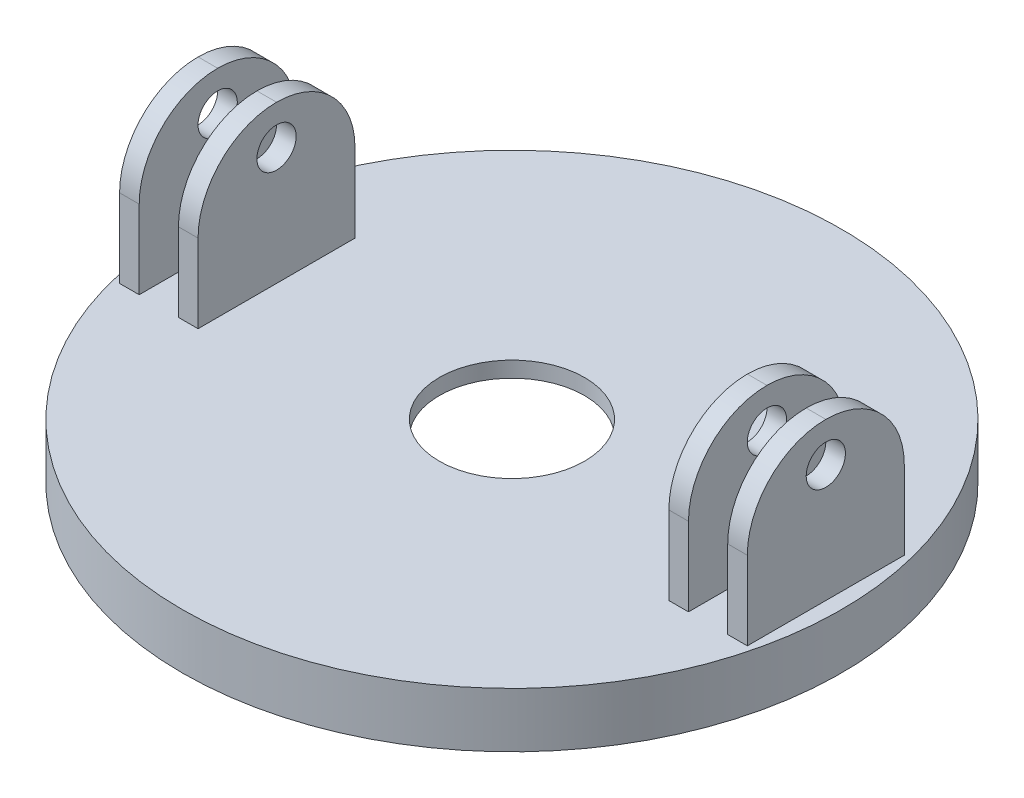
SolidWorks part; units mm, degrees
ref_plane "Alzado" through (0, 0, 0) normal (0, 0, 1) x (1, 0, 0)
ref_plane "Planta" through (0, 0, 0) normal (0, 1, 0) x (1, 0, 0)
ref_plane "Vista lateral" through (0, 0, 0) normal (1, 0, 0) x (0, 0, -1)
sketch "Croquis1" plane through (0, 0, 0) normal (0, 1, 0) x (1, 0, 0)
  circle A0 centre (0, 0) radius 84
  circle A1 centre (0, 0) radius 82
  dimension "D1" = 168
  dimension "D2" = 164
extrude "Saliente-Extruir1" add sketch "Croquis1" along normal blind 10
sketch "Croquis2" plane through (0, 10, 0) normal (0, 1, 0) x (1, 0, 0)
  circle A0 centre (0, 0) radius 84
  dimension "D1" = 168
extrude "Saliente-Extruir2" add sketch "Croquis2" along normal blind 4
sketch "Croquis3" plane through (0, 10, 0) normal (0, -1, 0) x (1, 0, 0)
  circle A0 centre (-20, 40) radius 1.5
  dimension "D1" = 3
  dimension "D6" = 40
  dimension "D7" = 20
extrude "Saliente-Extruir3" add sketch "Croquis3" along normal blind 10
ref_axis "Eje1" through (0, -0.7, 0) along (0, 1, 0)
pattern_circular "MatrizC1" count 4 every 90 about axis through (0, -0.7, 0) along (0, 1, 0) of "Saliente-Extruir3"
sketch "Croquis15" plane through (0, 0, 0) normal (0, -1, 0) x (1, 0, 0)
  circle A0 centre (0, 0) radius 82
  circle A1 centre (0, 0) radius 83
  dimension "D1" = 164
  dimension "D2" = 166
extrude "Cortar-Extruir1" cut sketch "Croquis15" against normal blind 5
sketch "Croquis16" plane through (0, 10, 0) normal (0, -1, 0) x (1, 0, 0)
  circle A0 centre (0, 0) radius 18.5
  dimension "D1" = 37
extrude "Cortar-Extruir2" cut sketch "Croquis16" against normal blind 13 contours A0
sketch "Croquis18" plane through (0, 14, 0) normal (0, 1, 0) x (1, 0, 0)
  line L0 (0, 0) -> (-84, 0) construction
  line L1 (0, 0) -> (0, 84) construction
  line L3 (-80, -20) -> (-60, -20)
  line L4 (-80, -20) -> (-80, 20)
  line L5 (-80, 20) -> (-60, 20)
  line L6 (-60, -20) -> (-60, 20)
  line L7 (-80, -20) -> (-60, 20) construction
  line L8 (-80, 20) -> (-60, -20) construction
  circle A0 centre (0, 0) radius 84 construction
  point P6 (-70, 0)
  dimension "D1" = 20
  dimension "D2" = 40
  dimension "D3" = 60
extrude "Saliente-Extruir4" add sketch "Croquis18" along normal blind 40
sketch "Croquis19" plane through (0, 54, 0) normal (0, 1, 0) x (1, 0, 0)
  line L0 (-60, 20) -> (-80, 20) construction
  line L1 (-75, 20) -> (-65, 20)
  line L2 (-75, 20) -> (-75, -20)
  line L3 (-75, -20) -> (-65, -20)
  line L4 (-65, 20) -> (-65, -20)
  line L5 (-80, -20) -> (-60, -20) construction
  line L6 (-80, 20) -> (-80, -20) construction
  dimension "D2" = 10
  dimension "D3" = 5
extrude "Cortar-Extruir3" cut sketch "Croquis19" against normal blind 40
sketch "Croquis20" plane through (-80, 0, 0) normal (-1, 0, 0) x (0, 0, 1)
  line L0 (-20, 54) -> (20, 54) construction
  line L1 (-20, 54) -> (-20, 14) construction
  circle A0 centre (0, 44) radius 5
  dimension "D3" = 10
  dimension "D1" = 10
  dimension "D2" = 20
extrude "Cortar-Extruir4" cut sketch "Croquis20" against normal blind 40
fillet "Redondeo2" radius 20 4 edges at (-77.5, 54, 20) (-62.5, 54, 20) (-62.5, 54, -20) (-77.5, 54, -20)
mirror "Simetría1" about plane through (0, 0, 0) normal (1, 0, 0) of "Saliente-Extruir4", "Redondeo2", "Cortar-Extruir4", "Cortar-Extruir3"
sketch "Croquis21" plane through (60, 0, 0) normal (-1, 0, 0) x (0, 0, 1)
  line L0 (-20, 34) -> (-20, 14) construction
  line L1 (20, 14) -> (-20, 14) construction
  circle A0 centre (0, 24) radius 5
  dimension "D2" = 10
  dimension "D3" = 10
  dimension "D1" = 20
extrude "Cortar-Extruir5" cut sketch "Croquis21" against normal blind 10
